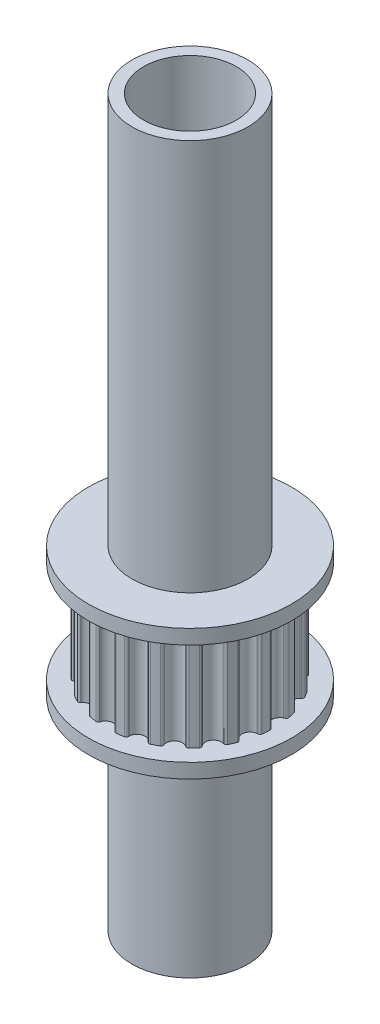
SolidWorks part; units mm, degrees
ref_plane "Front Plane" through (0, 0, 0) normal (0, 0, 1) x (1, 0, 0)
ref_plane "Top Plane" through (0, 0, 0) normal (0, 1, 0) x (1, 0, 0)
ref_plane "Right Plane" through (0, 0, 0) normal (1, 0, 0) x (0, 0, -1)
sketch "Sketch1" plane through (0, 0, 0) normal (0, 1, 0) x (1, 0, 0)
  circle A0 centre (0, 0) radius 4
  circle A1 centre (0, 0) radius 3.2
  dimension "D1" = 8
  dimension "D2" = 0.8
extrude "Boss-Extrude1" add sketch "Sketch1" along normal blind 50
ref_plane "Plane1" through (0, 15, 0) normal (0, 1, 0) x (1, 0, 0)
sketch "Sketch2" plane through (0, 15, 0) normal (0, 1, 0) x (1, 0, 0)
  circle A0 centre (0, 0) radius 6
  circle A1 centre (0, 0) radius 4
  dimension "D1" = 12
extrude "Boss-Extrude2" add sketch "Sketch2" along normal blind 7
sketch "Sketch3" plane through (0, 15, 0) normal (0, -1, 0) x (1, 0, 0)
  circle A0 centre (0, 0) radius 4
  circle A1 centre (0, 0) radius 7
  circle A2 centre (0, 0) radius 4 construction
  dimension "D1" = 14
extrude "Boss-Extrude3" add sketch "Sketch3" along normal blind 1 separate body
sketch "Sketch6" plane through (0, 15, 0) normal (0, 1, 0) x (1, 0, 0)
  line L0 (0, 0) -> (0, 8.1681) construction
  line L1 (-0.0071, -0.0407) -> (0.9465, 5.4303) construction
  line L2 (-0.0099, -0.04) -> (1.3906, 5.6439) construction
  line L3 (0, 5.795) -> (0, 6.6155)
  line L4 (1.9605, 5.4533) -> (2.2381, 6.2254)
  arc A1 (0.2982, 5.7873) -> (0, 5.795) centre (0, 0) ccw
  arc A2 (0.2982, 5.7873) -> (0.439, 5.6587) centre (0.2905, 5.6375) cw
  arc A3 (0.439, 5.6587) -> (0.4521, 5.586) centre (1.429, 5.7996) ccw
  arc A4 (0.4521, 5.586) -> (1.4644, 5.4096) centre (0.9943, 5.7045) ccw
  circle A5 centre (0, 0) radius 5.2355 construction
  circle A6 centre (0, 0) radius 5.795 construction
  arc A7 (-1.5827, -6.4234) -> (-1.1359, -6.5173) centre (0, 0) ccw
  arc A8 (1.5013, 5.4735) -> (1.4644, 5.4096) centre (0.6173, 5.941) cw
  arc A9 (1.6773, 5.5469) -> (1.5013, 5.4735) centre (1.6339, 5.4034) ccw
  arc A10 (1.6773, 5.5469) -> (1.9605, 5.4533) centre (0, 0) cw
  arc A11 (2.2381, 6.2254) -> (0, 6.6155) centre (0, 0) ccw
  circle A12 centre (0, 0) radius 6.6155 construction
  point P15 (1.3864, 5.6267)
  point P16 (0.995, 5.7089)
  point P18 (6.3265, 1.9342)
  dimension "D1" = 1.38
  dimension "D2" = 0.15
  dimension "D3" = 1
  dimension "D4" = 0.555
  dimension "D7" = 11.59
  dimension "D6" = 0.4
  dimension "D5" = 1.38
  dimension "D8" = 1
extrude "Cut-Extrude1" cut sketch "Sketch6" along normal blind 7 contours L4 A11 L3 A1 A2 A3 A4 A8 A9 A10 region at (1.0383, 15, -5.9574)
ref_axis "Axis1" through (0, 50, 0) along (0, -1, 0)
pattern_circular "CirPattern1" count 19 over 360 about axis through (0, 50, 0) along (0, -1, 0) of "Cut-Extrude1"
sketch "Sketch4" plane through (0, 22, 0) normal (0, 1, 0) x (1, 0, 0)
  circle A0 centre (0, 0) radius 7
  circle A1 centre (0, 0) radius 4
extrude "Boss-Extrude4" add sketch "Sketch4" along normal blind 1
